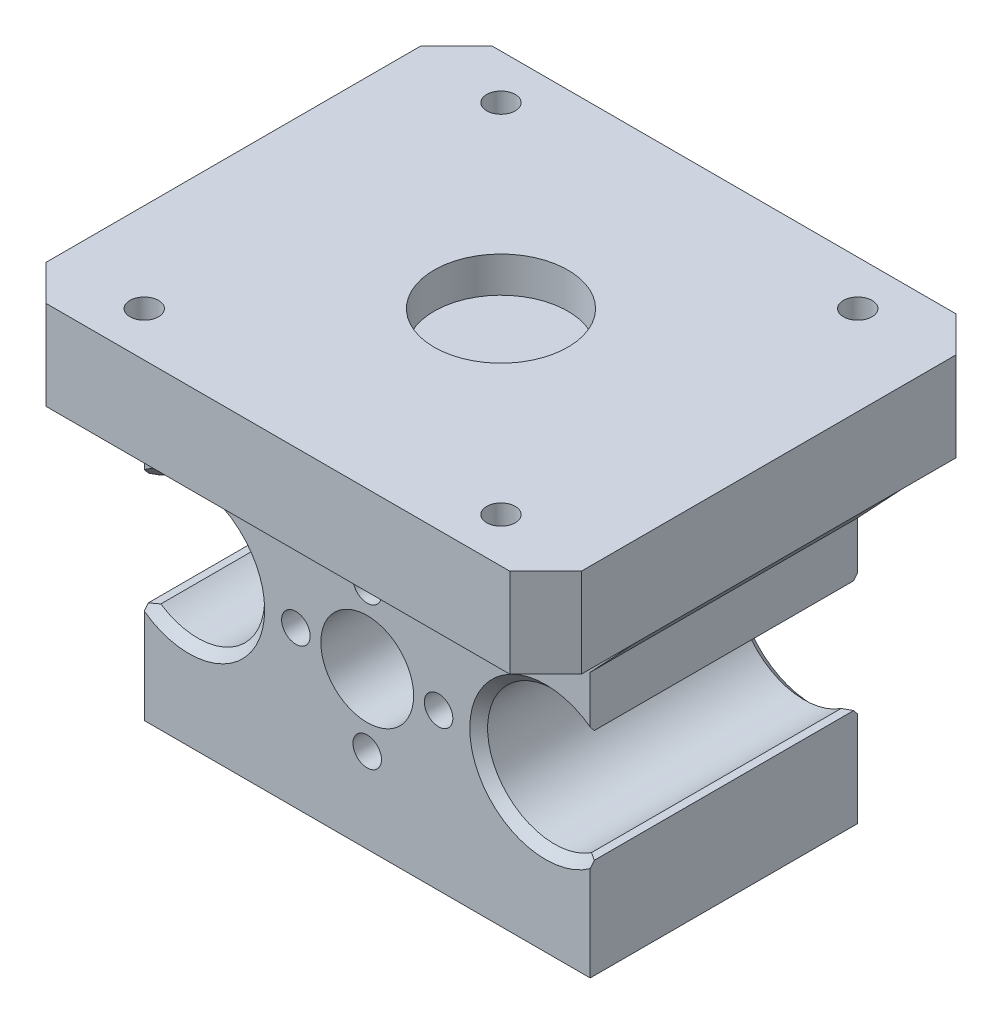
SolidWorks part; units mm, degrees
ref_plane "前视基准面" through (0, 0, 0) normal (0, 0, 1) x (1, 0, 0)
ref_plane "上视基准面" through (0, 0, 0) normal (0, 1, 0) x (1, 0, 0)
ref_plane "右视基准面" through (0, 0, 0) normal (1, 0, 0) x (0, 0, -1)
other "Configuration Table"
sketch "草图1" plane through (0, 0, 0) normal (0, 0, 1) x (1, 0, 0)
  line L1 (-25, -17.5) -> (25, -17.5)
  line L2 (-25, -17.5) -> (-25, 17.5)
  line L3 (-25, 17.5) -> (25, 17.5)
  line L4 (25, -17.5) -> (25, 17.5)
  line L5 (-25, -17.5) -> (25, 17.5) construction
  line L6 (-25, 17.5) -> (25, -17.5) construction
  point P0 (0, 0)
  dimension "D1" = 50
  dimension "D2" = 35
extrude "凸台-拉伸1" add sketch "草图1" along normal blind 30
hole_wizard "光轴孔" positions "草图2" profile "草图3" legacy end condition through all
sketch "草图2" plane through (0, 0, 30) normal (0, 0, 1) x (1, 0, 0)
  point P0 (0, 0)
sketch "草图3" plane through (0, 0, 30) normal (1, 0, 0) x (0, -1, 0)
  line L0 (0, 0) -> (0, 30)
  line L1 (0, 30) -> (4.25, 30)
  line L2 (4.25, 30) -> (4.25, 0)
  line L3 (4.25, 0) -> (0, 0)
  line L4 (0, 110) -> (0, -10) construction
  dimension "直径" = 8.5
  dimension "深度" = 30
hole_wizard "光轴座螺丝孔" positions "草图4" profile "草图5" legacy end condition through all
sketch "草图4" plane through (0, 0, 30) normal (0, 0, 1) x (1, 0, 0)
  point P0 (8, 0)
  point P4 (0, 8)
  point P6 (-8, 0)
  point P8 (0, -8)
  dimension "D1" = 8
  dimension "D2" = 8
  dimension "D3" = 8
  dimension "D4" = 8
sketch "草图5" plane through (8, 0, 30) normal (1, 0, 0) x (0, -1, 0)
  line L0 (0, 0) -> (0, 30)
  line L1 (0, 30) -> (1.6, 30)
  line L2 (1.6, 30) -> (1.6, 0)
  line L3 (1.6, 0) -> (0, 0)
  line L4 (0, 110) -> (0, -10) construction
  dimension "直径" = 3.2
  dimension "深度" = 30
hole_wizard "直线轴承座孔" positions "草图6" profile "草图7" legacy end condition through all
sketch "草图6" plane through (0, 0, 30) normal (0, 0, 1) x (1, 0, 0)
  point P0 (20, 0)
  point P2 (-20, 0)
  dimension "D1" = 20
  dimension "D2" = 20
sketch "草图7" plane through (20, 0, 30) normal (1, 0, 0) x (0, -1, 0)
  line L0 (0, 0) -> (0, 30)
  line L1 (0, 30) -> (7.5, 30)
  line L2 (7.5, 30) -> (7.5, 0)
  line L3 (7.5, 0) -> (0, 0)
  line L4 (0, 110) -> (0, -10) construction
  dimension "直径" = 15
  dimension "深度" = 30
chamfer "倒角1" distance 1 angle 45 8 edges at (25, -5.5902, 15) (12.5, 0, 30) (25, 5.5902, 15) (12.5, 0, 0) (-12.5, 0, 30) (-12.5, 0, 0) (-25, 5.5902, 15) (-25, -5.5902, 15) first distance on face at (18.75, 0, 15) first distance on face at (-18.75, 0, 15)
hole_wizard "孔1" positions "草图9" profile "草图10" legacy
sketch "草图9" plane through (0, 0, 30) normal (0, 0, 1) x (1, 0, 0)
  point P0 (0, 0)
sketch "草图10" plane through (0, 0, 30) normal (1, 0, 0) x (0, -1, 0)
  line L0 (0, 0) -> (0, 11)
  line L1 (0, 11) -> (5.2, 11)
  line L2 (5.2, 11) -> (5.2, 0)
  line L3 (5.2, 0) -> (0, 0)
  line L4 (0, 110) -> (0, -10) construction
  dimension "直径" = 10.4
  dimension "深度" = 11
sketch "草图11" plane through (0, 17.5, 0) normal (0, 1, 0) x (1, 0, 0)
  line L1 (-30, -40) -> (30, -40)
  line L2 (-30, -40) -> (-30, 10)
  line L3 (-30, 10) -> (30, 10)
  line L4 (30, -40) -> (30, 10)
  line L5 (-30, -40) -> (30, 10) construction
  line L6 (-30, 10) -> (30, -40) construction
  point P0 (0, -15)
  dimension "D1" = 60
  dimension "D2" = 50
extrude "凸台-拉伸3" add sketch "草图11" along normal blind 10
hole_wizard "孔2" positions "草图12" profile "草图13" legacy end condition through all
sketch "草图12" plane through (0, 27.5, 0) normal (0, 1, 0) x (1, 0, 0)
  point P0 (-20, 5)
  point P3 (20, 5)
  point P6 (20, -35)
  point P9 (-20, -35)
sketch "草图13" plane through (-20, 27.5, -5) normal (1, 0, 0) x (0, 0, 1)
  line L0 (0, 0) -> (0, 45)
  line L1 (0, 45) -> (1.6, 45)
  line L2 (1.6, 45) -> (1.6, 0)
  line L3 (1.6, 0) -> (0, 0)
  line L4 (0, 110) -> (0, -10) construction
  dimension "直径" = 3.2
  dimension "深度" = 45
chamfer "倒角2" distance 4 angle 45 4 edges at (-30, 22.5, -10) (30, 22.5, -10) (30, 22.5, 40) (-30, 22.5, 40)
hole_wizard "孔3" positions "草图14" profile "草图15" legacy
sketch "草图14" plane through (0, 27.5, 0) normal (0, 1, 0) x (1, 0, 0)
  point P0 (0, -15)
sketch "草图15" plane through (0, 27.5, 15) normal (1, 0, 0) x (0, 0, 1)
  line L0 (0, 0) -> (0, 4)
  line L1 (0, 4) -> (7.5, 4)
  line L2 (7.5, 4) -> (7.5, 0)
  line L3 (7.5, 0) -> (0, 0)
  line L4 (0, 110) -> (0, -10) construction
  dimension "直径" = 15
  dimension "深度" = 4
ref_plane "基准面1" through (0, 0, 0) normal (1, 0, 0) x (0, 0, -1)
ref_plane "基准面2" through (0, 0, 15) normal (0, 0, 1) x (1, 0, 0)
sketch "草图16" plane through (0, 0, 0) normal (1, 0, 0) x (0, 0, -1)
  line L0 (-40, 17.5) -> (-30, 12.5)
  line L1 (-30, 6.8739) -> (-30, 17.5) construction
  line L2 (-40, 17.5) -> (-30, 17.5)
  line L3 (-30, 17.5) -> (-30, 12.5)
  line L4 (-15, 19.25) -> (-15, -19.25) construction
  line L5 (10, 17.5) -> (0, 17.5)
  line L6 (10, 17.5) -> (0, 12.5)
  line L7 (0, 17.5) -> (0, 12.5)
  dimension "D1" = 5
extrude "凸台-拉伸4" add sketch "草图16" along normal mid plane 30
sketch "草图19" plane through (0, 0, 15) normal (0, 0, 1) x (1, 0, 0)
  line L0 (-30, 17.5) -> (-25, 12.1869)
  line L1 (-25, 17.5) -> (-25, 6.8739) construction
  point P5 (0, 0)
  point P6 (0, 0)
rib "筋22" sketch "草图19" sketch "草图19" thickness 30 extrusion direction parallel to sketch draft on no parameters "D1"=30
mirror "镜向1" about plane through (0, 0, 0) normal (1, 0, 0) of "筋22"
